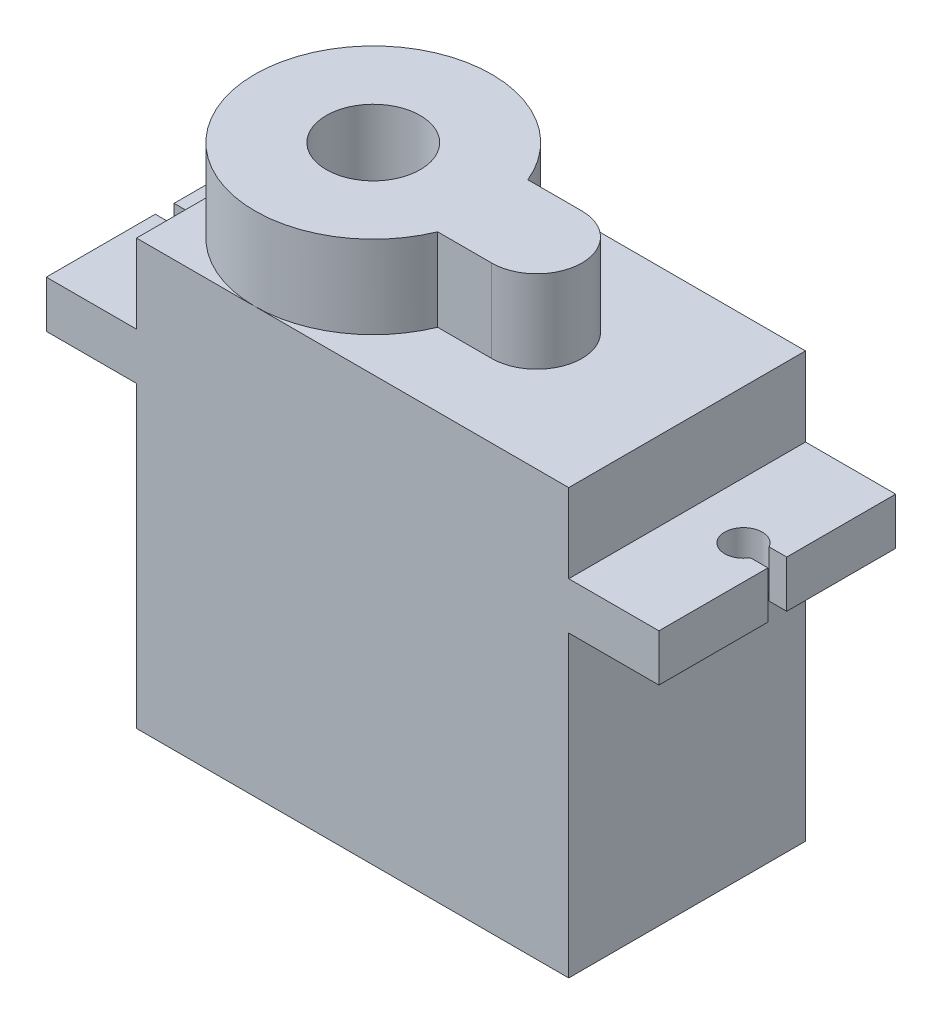
SolidWorks part; units mm, degrees
ref_plane "Alzado" through (0, 0, 0) normal (0, 0, 1) x (1, 0, 0)
ref_plane "Planta" through (0, 0, 0) normal (0, 1, 0) x (1, 0, 0)
ref_plane "Vista lateral" through (0, 0, 0) normal (1, 0, 0) x (0, 0, -1)
sketch "Croquis1" plane through (0, 0, 0) normal (0, 0, 1) x (1, 0, 0)
  line L0 (11.5, 0) -> (-11.5, 0)
  line L1 (-11.5, 0) -> (-11.5, 15.9)
  line L2 (-11.5, 15.9) -> (-16.3, 15.9)
  line L3 (-16.3, 15.9) -> (-16.3, 18.4)
  line L4 (-16.3, 18.4) -> (-11.5, 18.4)
  line L5 (-11.5, 18.4) -> (-11.5, 22.6)
  line L6 (-11.5, 22.6) -> (11.5, 22.6)
  line L8 (0, 35.0828) -> (0, -5.7212) construction
  line L9 (11.5, 0) -> (11.5, 15.9)
  line L10 (11.5, 15.9) -> (16.3, 15.9)
  line L11 (16.3, 15.9) -> (16.3, 18.4)
  line L12 (16.3, 18.4) -> (11.5, 18.4)
  line L13 (11.5, 18.4) -> (11.5, 22.6)
  dimension "D1" = 23
  dimension "D2" = 15.9
  dimension "D3" = 2.5
  dimension "D4" = 4.2
  dimension "D5" = 4.8
  dimension "D6" = 4.8
extrude "Saliente-Extruir1" add sketch "Croquis1" along normal blind 12.6 contours L1 L2 L3 L4 L5 L6 L13 L12 L11 L10 L9 L0
sketch "Croquis2" plane through (0, 18.4, 0) normal (0, 1, 0) x (1, 0, 0)
  line L0 (-16.3, -12.6) -> (-16.3, -6.8) construction
  line L1 (-16.3, -12.6) -> (-16.3, 0) construction
  line L2 (-16.3, -6.3) -> (16.3, -6.3) construction
  line L3 (16.3, -12.6) -> (16.3, 0) construction
  line L4 (-16.3, 0) -> (-16.3, -5.8) construction
  line L5 (-16.3, -6.8) -> (-15.366, -6.8)
  line L6 (-16.3, -5.8) -> (-15.366, -5.8)
  line L7 (0, 0) -> (0, -12.6) construction
  line L8 (-11.5, -12.6) -> (11.5, -12.6) construction
  line L9 (-16.3, -6.8) -> (-16.3, -5.8)
  line L10 (-15.366, -5.8) -> (-15.366, -6.8)
  line L11 (15.366, -5.8) -> (15.366, -6.8)
  line L12 (16.3, -5.8) -> (15.366, -5.8)
  line L13 (16.3, -6.8) -> (16.3, -5.8)
  line L14 (16.3, -6.8) -> (15.366, -6.8)
  line L15 (-13.5, -6.3) -> (-13.5, -4.3984) construction
  line L16 (-11.503, -6.3) -> (-11.5, -4.3984) construction
  line L17 (-11.5, -12.6) -> (-11.5, 0) construction
  line L18 (-11.5, -12.6) -> (-11.5, 0) construction
  line L19 (-16.3, -12.6) -> (-11.5, -12.6) construction
  circle A0 centre (-14.5, -6.3) radius 1
  circle A1 centre (14.5, -6.3) radius 1
  point P12 (-14.5, -6.3)
  dimension "D4" = 1
  dimension "D1" = 5.8
  dimension "D2" = 2
  dimension "D3" = 1.8
extrude "Cortar-Extruir2" cut sketch "Croquis2" against normal blind 2.5 contours A1 L14 L12 | L11 A1 | L11 A1 | L5 A0 L6 L9 | A0 L10 | A0 L10 region at (-15.8774, 18.4, 6.3) region at (-15.4199, 18.4, 6.3) region at (-14.4727, 18.4, 6.3) region at (15.4199, 18.4, 6.3) region at (15.8774, 18.4, 6.3) region at (14.4727, 18.4, 6.3)
sketch "Croquis4" plane through (0, 22.6, 0) normal (0, 1, 0) x (1, 0, 0)
  line L0 (-11.5, -6.3) -> (-5.2, -6.3) construction
  line L1 (-11.5, -12.6) -> (-11.5, 0) construction
  line L2 (-5.2, -6.3) -> (3.5, -6.3) construction
  line L4 (-1.3, -8.7) -> (3.5, -8.7)
  line L5 (-1.3, -8.7) -> (-1.3, -3.9)
  line L6 (-1.3, -3.9) -> (3.5, -3.9)
  line L7 (3.5, -8.7) -> (3.5, -3.9)
  line L8 (-1.3, -8.7) -> (3.5, -3.9) construction
  line L9 (-1.3, -3.9) -> (3.5, -8.7) construction
  circle A0 centre (-5.2, -6.3) radius 6.3
  circle A1 centre (3.5, -6.3) radius 2.4
  circle A2 centre (-5.2, -6.3) radius 2.5
  point P7 (1.1, -6.3)
  point P8 (1.1, -6.3)
  dimension "D2" = 12.6
  dimension "D4" = 4.8
  dimension "D5" = 5
  dimension "D1" = 6.3
  dimension "D3" = 8.7
extrude "Saliente-Extruir4" add sketch "Croquis4" along normal blind 4.4 contours A0 L4 L5 L6 A2 | L7 A1 | L7 A1 | A1 A0 L4 | A1 L6 A0 | L4 A0 L6 L5 region at (-0.1735, 22.6, 6.3) region at (-0.3375, 22.6, 8.8749) region at (1.4786, 22.6, 8.1501) region at (2.4814, 22.6, 6.3) region at (4.5186, 22.6, 6.3) region at (1.4786, 22.6, 4.4499)
